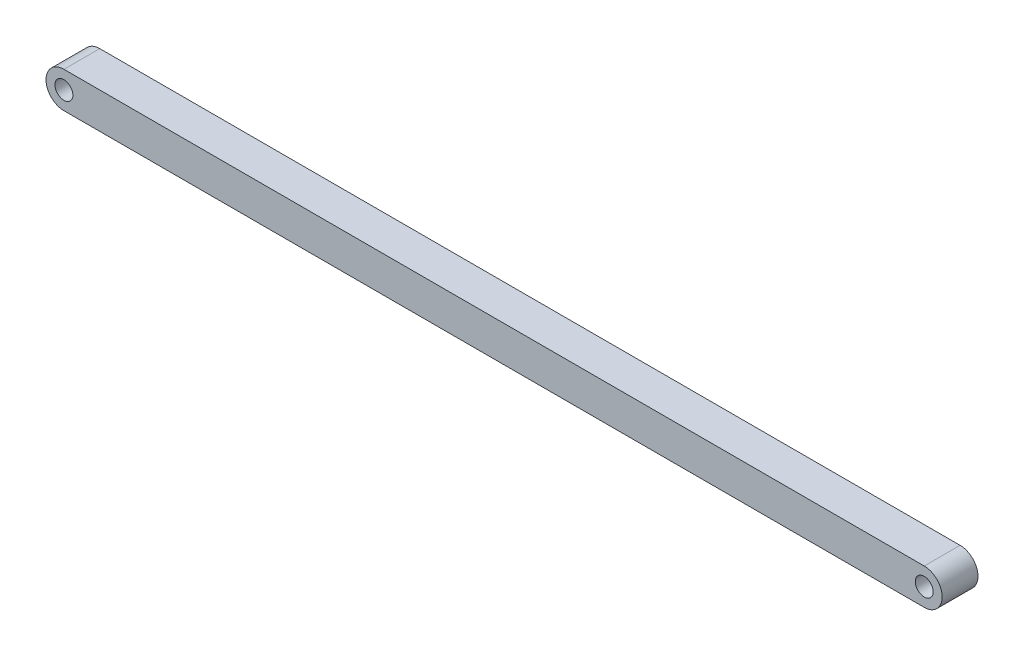
SolidWorks part; units mm, degrees
ref_plane "Front Plane" through (0, 0, 0) normal (0, 0, 1) x (1, 0, 0)
ref_plane "Top Plane" through (0, 0, 0) normal (0, 1, 0) x (1, 0, 0)
ref_plane "Right Plane" through (0, 0, 0) normal (1, 0, 0) x (0, 0, -1)
sketch "Sketch1" plane through (0, 0, 0) normal (0, 0, 1) x (1, 0, 0)
  line L0 (-304.8, 0) -> (304.8, 0) construction
  line L1 (-304.8, 12.7) -> (304.8, 12.7)
  line L2 (-304.8, -12.7) -> (304.8, -12.7)
  arc A0 (-304.8, 12.7) -> (-304.8, -12.7) centre (-304.8, 0) ccw
  arc A1 (304.8, -12.7) -> (304.8, 12.7) centre (304.8, 0) ccw
  point P3 (0, 0)
  dimension "D1" = 25.4
  dimension "D2" = 609.6
extrude "Boss-Extrude1" add sketch "Sketch1" along normal mid plane 25.4
sketch "Sketch2" plane through (0, 0, 12.7) normal (0, 0, 1) x (1, 0, 0)
  line L2 (-304.8, -12.7) -> (304.8, -12.7)
  line L3 (304.8, 12.7) -> (-304.8, 12.7)
  line L4 (-304.8, -12.7) -> (304.8, -12.7)
  line L5 (304.8, 12.7) -> (-304.8, 12.7)
  circle A0 centre (-304.8, 0) radius 6.35
  circle A1 centre (304.8, 0) radius 6.35
  arc A2 (-304.8, 12.7) -> (-304.8, -12.7) centre (-304.8, 0) ccw
  arc A3 (304.8, -12.7) -> (304.8, 12.7) centre (304.8, 0) ccw
  arc A4 (-304.8, 12.7) -> (-304.8, -12.7) centre (-304.8, 0) ccw
  arc A5 (304.8, -12.7) -> (304.8, 12.7) centre (304.8, 0) ccw
  dimension "D2" = 12.7
  dimension "D3" = 12.7
  dimension "D1" = 0
extrude "Cut-Extrude1" cut sketch "Sketch2" against normal through all contours A0 | A1 region at (-304.8, 0, 12.7) region at (304.8, 0, 12.7)
